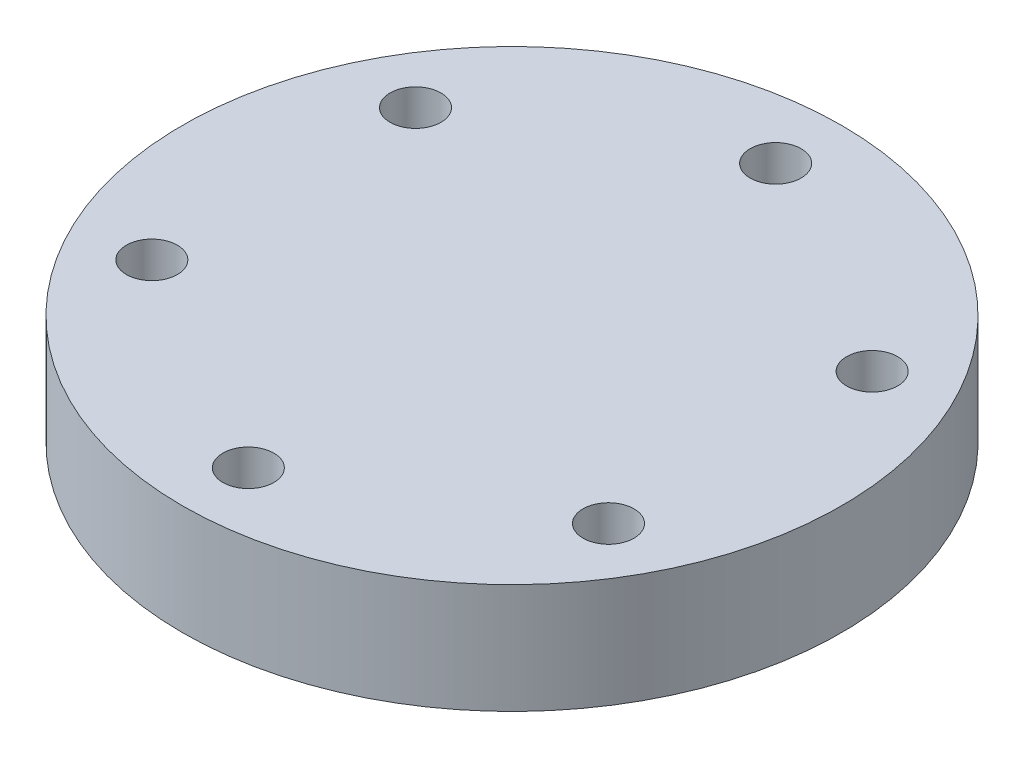
SolidWorks part; units mm, degrees
material "Copper"
ref_plane "Front Plane" through (0, 0, 0) normal (0, 0, 1) x (1, 0, 0)
ref_plane "Top Plane" through (0, 0, 0) normal (0, 1, 0) x (1, 0, 0)
ref_plane "Right Plane" through (0, 0, 0) normal (1, 0, 0) x (0, 0, -1)
ref_axis "Y Axis" through (0, 6.6675, 0) along (0, -1, 0)
sketch "outer" plane through (0, 0, 0) normal (0, 1, 0) x (1, 0, 0)
  circle A0 centre (0, 0) radius 19.05
  dimension "D1" = 38.1
extrude "Body" add sketch "outer" along normal blind 6.35
sketch "inner" plane through (0, 0, 0) normal (0, 1, 0) x (1, 0, 0)
  circle A0 centre (0, 0) radius 11.6205
  dimension "D1" = 23.241
extrude "Pocket" cut sketch "inner" along normal blind 3.81
sketch "Screw Position" plane through (0, 0, 0) normal (0, 1, 0) x (1, 0, 0)
  point P0 (0, 15.24)
hole_wizard "#32 (0.116) Diameter Hole1" positions "Sketch7" profile "Sketch8" hole size "#32" standard "ANSI Inch" end condition through all
sketch "Sketch7" plane through (0, 6.35, 0) normal (0, 1, 0) x (1, 0, 0)
  point P0 (0, 15.24)
sketch "Sketch8" plane through (0, 6.35, -15.24) normal (1, 0, 0) x (0, 0, 1)
  line L0 (0, 0) -> (0, 6.35)
  line L1 (0, 6.35) -> (1.4732, 6.35)
  line L2 (1.4732, 6.35) -> (1.4732, 0)
  line L5 (1.4732, 0) -> (0, 0)
  line L11 (0, -6.35) -> (0, 107.95) construction
  dimension "Thru Hole Dia." = 2.9464
  dimension "Thru Hole Depth" = 6.35
pattern_circular "Screw Holes" count 6 over 360 about axis through (0, 6.6675, 0) along (0, -1, 0) of "#32 (0.116) Diameter Hole1"
equation "\"outer_d\"= 3 / 2in"
equation "\"top_h\"= 1 / 4in"
equation "\"screw_r\"= 0.6in"
equation "\"inner_d\"= 0.915in"
equation "\"inner_h\"= 150mil"
equation "\"D1@outer\" = \"outer_d\""
equation "\"D1@Body\" = \"top_h\""
equation "\"D1@inner\"=\"inner_d\""
equation "\"D1@Pocket\" = \"inner_h\""
equation "\"D1@Screw Position\"=\"screw_r\""
